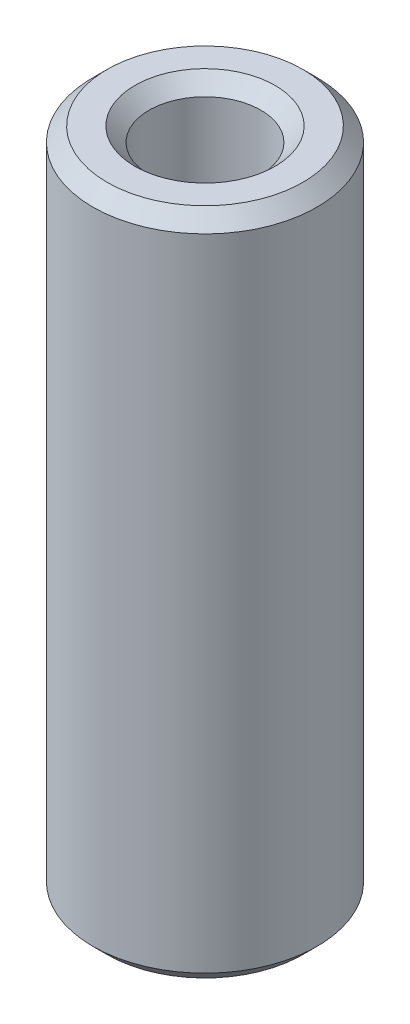
SolidWorks part; units mm, degrees
ref_plane "Front Plane" through (0, 0, 0) normal (0, 0, 1) x (1, 0, 0)
ref_plane "Top Plane" through (0, 0, 0) normal (0, 1, 0) x (1, 0, 0)
ref_plane "Right Plane" through (0, 0, 0) normal (1, 0, 0) x (0, 0, -1)
sketch "Sketch1" plane through (0, 0, 0) normal (0, 1, 0) x (1, 0, 0)
  circle A0 centre (0, 0) radius 7.5
  dimension "SLEEVE_OD" = 15
extrude "Boss-Extrude1" add sketch "Sketch1" along normal blind 44.7276
sketch "Sketch2" plane through (0, 0, 0) normal (0, 1, 0) x (1, 0, 0)
  circle A0 centre (0, 0) radius 3.7349
  dimension "BORE_D" = 7.4698
extrude "Cut-Extrude1" cut sketch "Sketch2" along normal through all
chamfer "Chamfer1" distance 0.9551 angle 45 4 edges at (0, 44.7276, 3.7349) (0, 0, 3.7349) (0, 0, 7.5) (0, 44.7276, 7.5)
